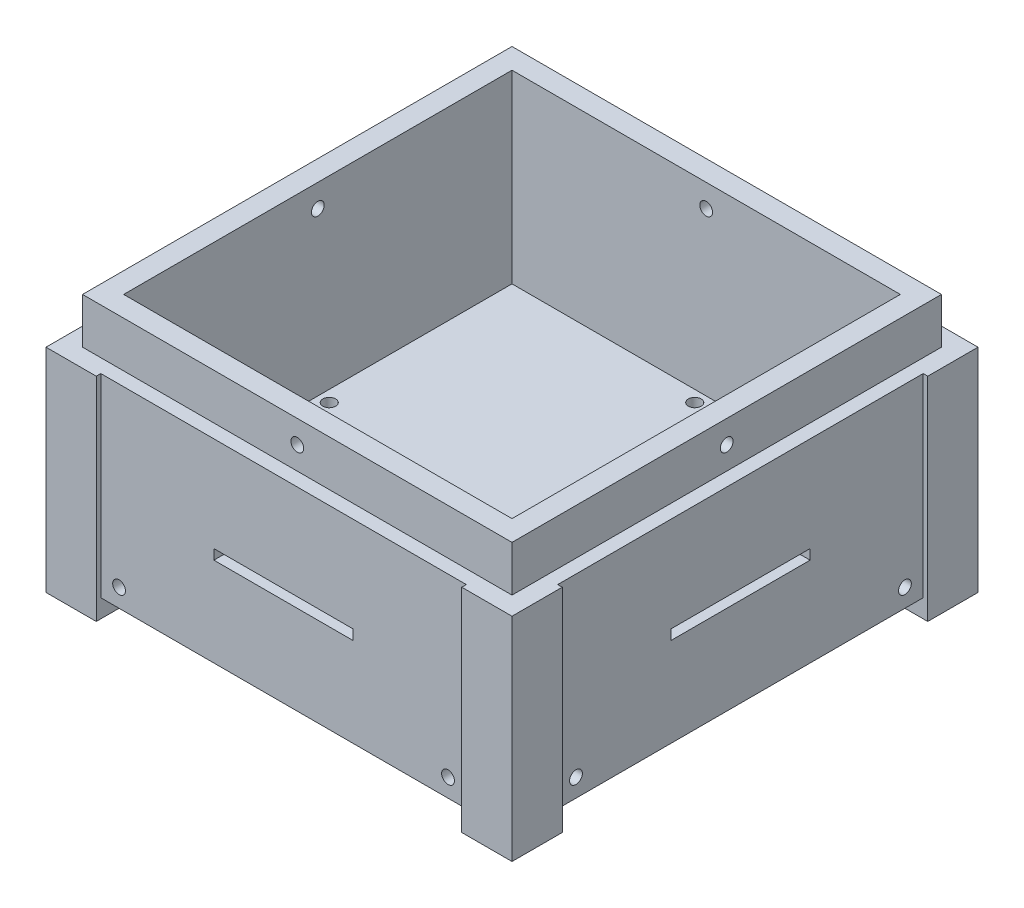
SolidWorks part; units mm, degrees
ref_plane "Front Plane" through (0, 0, 0) normal (0, 0, 1) x (1, 0, 0)
ref_plane "Top Plane" through (0, 0, 0) normal (0, 1, 0) x (1, 0, 0)
ref_plane "Right Plane" through (0, 0, 0) normal (1, 0, 0) x (0, 0, -1)
sketch "Sketch1" plane through (0, 0, 0) normal (0, 1, 0) x (1, 0, 0)
  line L1 (-50, 50) -> (50, 50)
  line L2 (-50, 50) -> (-50, -50)
  line L3 (-50, -50) -> (50, -50)
  line L4 (50, 50) -> (50, -50)
  line L5 (-50, 50) -> (50, -50) construction
  line L6 (-50, -50) -> (50, 50) construction
  point P0 (0, 0)
  dimension "D1" = 100
  dimension "D2" = 100
extrude "Boss-Extrude1" add sketch "Sketch1" along normal blind 95
ref_plane "Plane1" through (0, 100, 0) normal (0, 1, 0) x (1, 0, 0)
sketch "Sketch2" plane through (0, 100, 0) normal (0, 1, 0) x (1, 0, 0)
  line L0 (0, 0) -> (0, 71.0273) construction
  line L1 (-50, 50) -> (-40, 50)
  line L2 (-50, 50) -> (-50, 40)
  line L3 (-50, 40) -> (-40, 40)
  line L4 (-40, 50) -> (-40, 40)
  line L5 (50, 40) -> (40, 40)
  line L6 (40, 50) -> (40, 40)
  line L7 (50, 50) -> (40, 50)
  line L8 (50, 50) -> (50, 40)
  line L9 (0, 0) -> (-74.2097, 0) construction
  line L10 (50, -50) -> (50, -40)
  line L11 (50, -50) -> (40, -50)
  line L12 (40, -50) -> (40, -40)
  line L13 (50, -40) -> (40, -40)
  line L14 (-50, -40) -> (-40, -40)
  line L15 (-40, -50) -> (-40, -40)
  line L16 (-50, -50) -> (-40, -50)
  line L17 (-50, -50) -> (-50, -40)
  dimension "D1" = 10
  dimension "D2" = 10
extrude "Boss-Extrude2" add sketch "Sketch2" against normal blind 105
sketch "Sketch3" plane through (0, 95, 0) normal (0, 1, 0) x (1, 0, 0)
  line L0 (0, 0) -> (-55.4811, 0) construction
  line L1 (0, 0) -> (0, -56.887) construction
  line L3 (50, -40) -> (40, -40) construction
  circle A0 centre (-28, -45) radius 1.4
  circle A1 centre (28, -45) radius 1.4
  circle A2 centre (28, 45) radius 1.4
  circle A3 centre (-28, 45) radius 1.4
  dimension "D1" = 2.8
  dimension "D2" = 28
  dimension "D3" = 85
extrude "Cut-Extrude1" cut sketch "Sketch3" against normal blind 10
sketch "Sketch4" plane through (0, 100, 0) normal (0, 1, 0) x (1, 0, 0)
  line L0 (-50, 50) -> (-50, 40) construction
  line L1 (-40, 40) -> (-51, 40)
  line L2 (-40, 40) -> (-40, 51)
  line L3 (-40, 51) -> (-51, 51)
  line L4 (-51, 40) -> (-51, 51)
  line L5 (40, 50) -> (-40, 50) construction
  line L6 (0, 0) -> (0, 60.0537) construction
  line L7 (0, 0) -> (-61.4769, 0) construction
  line L8 (40, 51) -> (51, 51)
  line L9 (51, 40) -> (51, 51)
  line L10 (40, 40) -> (51, 40)
  line L11 (40, 40) -> (40, 51)
  line L12 (40, -40) -> (40, -51)
  line L13 (40, -40) -> (51, -40)
  line L14 (51, -40) -> (51, -51)
  line L15 (40, -51) -> (51, -51)
  line L16 (-40, -51) -> (-51, -51)
  line L17 (-51, -40) -> (-51, -51)
  line L18 (-40, -40) -> (-51, -40)
  line L19 (-40, -40) -> (-40, -51)
  dimension "D1" = 1
  dimension "D2" = 1
extrude "Boss-Extrude3" add sketch "Sketch4" against normal up to surface (105 mm away) up to face at (-45, -5, -45)
sketch "Sketch5" plane through (0, 0, 50) normal (0, 0, 1) x (1, 0, 0)
  line L0 (0, 95) -> (0, 43.7031) construction
  line L1 (-40, 95) -> (40, 95) construction
  line L2 (40, 47.5) -> (-59.8843, 47.5) construction
  line L3 (40, 0) -> (40, 95) construction
  line L4 (-40, 95) -> (-40, 0) construction
  circle A0 centre (-36, 91) radius 1.4
  circle A1 centre (36, 91) radius 1.4
  circle A2 centre (36, 4) radius 1.4
  circle A3 centre (-36, 4) radius 1.4
  dimension "D1" = 2.8
  dimension "D2" = 4
  dimension "D3" = 4
extrude "Cut-Extrude2" cut sketch "Sketch5" against normal blind 10
mirror "Mirror1" about plane through (0, 0, 0) normal (0, 0, 1) of "Cut-Extrude2"
sketch "Sketch6" plane through (-50, 0, 0) normal (-1, 0, 0) x (0, 0, 1)
  line L0 (-40, 95) -> (-40, 0) construction
  line L1 (-40, 95) -> (40, 95) construction
  line L2 (0, 95) -> (0, 40.4022) construction
  line L3 (-40, 47.5) -> (36.0105, 47.5) construction
  line L4 (-40, -5) -> (-40, 100) construction
  circle A0 centre (-36, 91) radius 1.4
  circle A1 centre (36, 91) radius 1.4
  circle A2 centre (36, 4) radius 1.4
  circle A3 centre (-36, 4) radius 1.4
  dimension "D1" = 2.8
  dimension "D2" = 4
  dimension "D3" = 4
extrude "Cut-Extrude3" cut sketch "Sketch6" against normal blind 10
mirror "Mirror2" about plane through (0, 0, 0) normal (1, 0, 0) of "Cut-Extrude3"
ref_plane "Plane2" through (0, 47.5, 0) normal (0, 1, 0) x (1, 0, 0)
mirror "Mirror3" about plane through (0, 47.5, 0) normal (0, 1, 0) of "Cut-Extrude1"
chamfer "Chamfer1" distance 1 angle 45 33 edges at (-45.5, -5, 51) (-40, -5, 45.5) (-45.5, -5, 40) (-51, -5, 45.5) (40, -5, 45.5) (45.5, -5, 51) (51, -5, 45.5) (45.5, -5, 40) (45.5, -5, -51) (40, -5, -45.5) (45.5, -5, -40) (51, -5, -45.5) (-40, -5, -45.5) (-45.5, -5, -51) (-51, -5, -45.5) (-45.5, -5, -40) (45.5, 100, 51) (40, 100, 45.5) (45.5, 100, 40) (51, 100, 45.5) (40, 100, -45.5) (45.5, 100, -51) (51, 100, -45.5) (45.5, 100, -40) (-45.5, 100, -40) (-51, 100, -45.5) (-45.5, 100, -51) (-40, 100, -45.5) (-40, 100, 45.5) (-45.5, 100, 51) (-51, 100, 45.5) (-45.5, 100, 40) (45, 95, -40)
sketch "Sketch7" plane through (0, 95, 0) normal (0, 1, 0) x (1, 0, 0)
  line L0 (9.5, 4.5) -> (9.5, -38.5)
  line L1 (-8, 3) -> (8, 3)
  line L2 (-8, 3) -> (-8, -37)
  line L3 (-8, -37) -> (8, -37)
  line L4 (8, 3) -> (8, -37)
  line L5 (-9.5, -38.5) -> (9.5, -38.5)
  line L6 (-9.5, 4.5) -> (-9.5, -38.5)
  line L7 (-9.5, 4.5) -> (9.5, 4.5)
  dimension "D1" = 8
  dimension "D2" = 8
  dimension "D3" = 3
  dimension "D4" = 40
  dimension "D5" = 1.5
extrude "Boss-Extrude4" add sketch "Sketch7" along normal blind 3
sketch "Sketch8" plane through (0, 95, 0) normal (0, 1, 0) x (1, 0, 0)
  line L4 (-8, 3) -> (-8, -37)
  line L5 (-8, -37) -> (8, -37)
  line L6 (8, -37) -> (8, 3)
  line L7 (8, 3) -> (-8, 3)
  line L8 (-8, 3) -> (-8, -37)
  line L9 (-8, -37) -> (8, -37)
  line L10 (8, -37) -> (8, 3)
  line L11 (8, 3) -> (-8, 3)
  dimension "D1" = 0
extrude "Cut-Extrude4" cut sketch "Sketch8" against normal blind 10
chamfer "Chamfer2" distance 13 angle 45 1 edges at (0, 85, 37)
sketch "Sketch9" plane through (0, 85, 0) normal (0, 1, 0) x (1, 0, 0)
  line L0 (8, -24) -> (8, 3) construction
  line L1 (-8, 3) -> (8, 3)
  line L2 (-8, 3) -> (-8, -0.1)
  line L3 (-8, -0.1) -> (8, -0.1)
  line L4 (8, 3) -> (8, -0.1)
  dimension "D1" = 3.1
extrude "Cut-Extrude5" cut sketch "Sketch9" against normal blind 10
fillet "Fillet1" radius 1 1 edges at (0, 85, 0.1)
sketch "Sketch10" plane through (0, 0, -3) normal (0, 0, 1) x (1, 0, 0)
  line L0 (8, 98) -> (-8, 98) construction
  line L1 (-8, 98) -> (-8, 75) construction
  circle A0 centre (0, 92) radius 1.4
  dimension "D1" = 2.8
  dimension "D2" = 6
  dimension "D3" = 8
extrude "Cut-Extrude6" cut sketch "Sketch10" against normal blind 10
sketch "Sketch12" plane through (-50, 0, 0) normal (-1, 0, 0) x (0, 0, 1)
  line L0 (-40, 95) -> (40, 95) construction
  line L1 (-15.25, 75.5) -> (15.25, 75.5)
  line L2 (-15.25, 75.5) -> (-15.25, 73.3)
  line L3 (-15.25, 73.3) -> (15.25, 73.3)
  line L4 (15.25, 75.5) -> (15.25, 73.3)
  line L5 (-15.25, 75.5) -> (15.25, 73.3) construction
  line L6 (-15.25, 73.3) -> (15.25, 75.5) construction
  line L7 (0, 95) -> (0, 60.126) construction
  line L8 (-51, 47.5) -> (62.2361, 47.5) construction
  line L9 (-51, -4) -> (-51, 99) construction
  line L10 (-15.25, 21.7) -> (15.25, 21.7)
  line L11 (15.25, 19.5) -> (15.25, 21.7)
  line L12 (-15.25, 19.5) -> (15.25, 19.5)
  line L13 (-15.25, 19.5) -> (-15.25, 21.7)
  line L14 (-40, 0) -> (40, 0) construction
  point P0 (0, 74.4)
  dimension "D1" = 19.5
  dimension "D2" = 2.2
  dimension "D3" = 30.5
extrude "Cut-Extrude7" cut sketch "Sketch12" against normal blind 3
mirror "Mirror4" about plane through (0, 0, 0) normal (1, 0, 0) of "Cut-Extrude7"
sketch "Sketch13" plane through (0, 0, 50) normal (0, 0, 1) x (1, 0, 0)
  line L0 (0, 95) -> (0, 46.2553) construction
  line L1 (-40, 95) -> (40, 95) construction
  line L2 (-51, 47.5) -> (61.8656, 47.5) construction
  line L3 (-15.25, 75.5) -> (15.25, 75.5)
  line L4 (-15.25, 75.5) -> (-15.25, 73.3)
  line L5 (-15.25, 73.3) -> (15.25, 73.3)
  line L6 (15.25, 75.5) -> (15.25, 73.3)
  line L7 (-15.25, 75.5) -> (15.25, 73.3) construction
  line L8 (-15.25, 73.3) -> (15.25, 75.5) construction
  line L9 (-51, -4) -> (-51, 99) construction
  line L10 (-15.25, 21.7) -> (15.25, 21.7)
  line L11 (15.25, 19.5) -> (15.25, 21.7)
  line L12 (-15.25, 19.5) -> (15.25, 19.5)
  line L13 (-15.25, 19.5) -> (-15.25, 21.7)
  point P5 (0, 74.4)
  dimension "D1" = 30.5
  dimension "D2" = 2.2
  dimension "D3" = 19.5
extrude "Cut-Extrude8" cut sketch "Sketch13" against normal blind 3
mirror "Mirror5" about plane through (0, 0, 0) normal (0, 0, 1) of "Cut-Extrude8"
sketch "Sketch14" plane through (0, 95, 0) normal (0, 1, 0) x (1, 0, 0)
  line L0 (-50, 0) -> (73.3052, 0) construction
  line L1 (-50, 40) -> (-50, -40) construction
  line L2 (0, 50) -> (0, -6.1969) construction
  line L3 (40, 50) -> (-40, 50) construction
  line L4 (28, 15.25) -> (25.8, 15.25)
  line L5 (-28, -15.25) -> (-25.8, -15.25)
  line L6 (-28, -15.25) -> (-28, 15.25)
  line L7 (-28, 15.25) -> (-25.8, 15.25)
  line L8 (-25.8, -15.25) -> (-25.8, 15.25)
  line L9 (-28, -15.25) -> (-25.8, 15.25) construction
  line L10 (-28, 15.25) -> (-25.8, -15.25) construction
  line L11 (25.8, -15.25) -> (25.8, 15.25)
  line L12 (28, -15.25) -> (25.8, -15.25)
  line L13 (28, -15.25) -> (28, 15.25)
  point P9 (-26.9, 0)
  dimension "D1" = 30.5
  dimension "D2" = 2.2
  dimension "D3" = 22
extrude "Cut-Extrude9" cut sketch "Sketch14" against normal blind 3
mirror "Mirror6" about plane through (0, 47.5, 0) normal (0, 1, 0) of "Cut-Extrude9"
sketch "Sketch15" plane through (0, 0, 0) normal (1, 0, 0) x (0, 0, -1)
  line L0 (-40, 0) -> (40, 0) construction
  line L1 (-45, 70) -> (45, 70)
  line L2 (-45, 70) -> (-45, 12)
  line L3 (-45, 12) -> (45, 12)
  line L4 (45, 70) -> (45, 12)
  line L5 (-45, 70) -> (45, 12) construction
  line L6 (-45, 12) -> (45, 70) construction
  line L7 (-51, -4) -> (-51, 99) construction
  line L8 (51, -4) -> (51, 99) construction
  line L9 (-40, 95) -> (39, 95) construction
  point P0 (0, 41)
  dimension "D1" = 12
  dimension "D2" = 6
  dimension "D3" = 6
  dimension "D4" = 25
extrude "Cut-Extrude10" cut sketch "Sketch15" against normal offset from surface 6 and the other way offset from surface 6 up to face at (-51, 47.5, -45.5) other way up to face at (51, 47.5, 45.5)
sketch "Sketch16" plane through (0, 0, 0) normal (0, 0, 1) x (1, 0, 0)
  line L0 (45, 57.0064) -> (-45, 57.0064)
  line L1 (51, -4) -> (51, 99) construction
  line L2 (-51, -4) -> (-51, 99) construction
  line L3 (45, 57.0064) -> (45, 83)
  line L4 (45, 83) -> (13, 83)
  line L5 (13, 83) -> (13, 67.0064)
  line L6 (13, 67.0064) -> (-13, 67.0064)
  line L7 (-13, 67.0064) -> (-13, 83)
  line L8 (-13, 83) -> (-45, 83)
  line L9 (-45, 83) -> (-45, 57.0064)
  line L10 (-40, 95) -> (40, 95) construction
  dimension "D1" = 6
  dimension "D2" = 6
  dimension "D3" = 57.0064
  dimension "D4" = 12
  dimension "D5" = 32
  dimension "D7" = 10
extrude "Cut-Extrude11" cut sketch "Sketch16" along normal up to surface and the other way up to surface up to face at (0, 41, 45) other way up to face at (0, 41, -45)
chamfer "Chamfer3" distance 4 angle 45 2 edges at (-13, 70, 0) (13, 70, 0)
sketch "Sketch17" plane through (0, 0, -51) normal (0, 0, -1) x (-1, 0, 0)
  line L0 (-51, -4) -> (-51, 99) construction
  line L2 (-51, 47.5) -> (-51, 104.9128)
  line L3 (-51, 104.9128) -> (51, 104.9128)
  line L4 (51, 47.5) -> (51, 104.9128)
  line L6 (40, -4) -> (51, -4) construction
  line L7 (-51, 47.5) -> (-51, 42.5)
  line L8 (-51, 42.5) -> (51, 42.5)
  line L9 (51, -4) -> (51, 99) construction
  line L10 (51, 42.5) -> (51, 47.5)
  dimension "D2" = 108.9128
  dimension "D3" = 46.5
extrude "Cut-Extrude12" cut sketch "Sketch17" against normal through all
sketch "Sketch19" plane through (0, 42.5, 0) normal (0, 1, 0) x (1, 0, 0)
  line L1 (-47, -47) -> (47, -47)
  line L2 (-47, -47) -> (-47, 47)
  line L3 (-47, 47) -> (47, 47)
  line L4 (47, -47) -> (47, 47)
  line L5 (-47, -47) -> (47, 47) construction
  line L6 (-47, 47) -> (47, -47) construction
  line L7 (-42.5, 42.5) -> (42.5, 42.5)
  line L8 (-42.5, 42.5) -> (-42.5, -42.5)
  line L9 (-42.5, -42.5) -> (42.5, -42.5)
  line L10 (42.5, 42.5) -> (42.5, -42.5)
  line L11 (-42.5, 42.5) -> (42.5, -42.5) construction
  line L12 (-42.5, -42.5) -> (42.5, 42.5) construction
  point P0 (0, 0)
  point P6 (0, 0)
  dimension "D1" = 94
  dimension "D2" = 94
  dimension "D3" = 85
  dimension "D4" = 85
extrude "Boss-Extrude7" add sketch "Sketch19" against normal up to surface (30.5 mm away) and the other way blind 10 up to face at (0, 12, 0)
sketch "Sketch20" plane through (0, 0, 47) normal (0, 0, 1) x (1, 0, 0)
  line L0 (-47, 52.5) -> (47, 52.5) construction
  line L1 (-47, 52.5) -> (-47, 42.5) construction
  circle A0 centre (0, 47.5) radius 1.4
  dimension "D1" = 2.8
  dimension "D2" = 5
  dimension "D3" = 47
extrude "Cut-Extrude13" cut sketch "Sketch20" against normal through all
sketch "Sketch21" plane through (47, 0, 0) normal (1, 0, 0) x (0, 0, -1)
  line L0 (-47, 52.5) -> (47, 52.5) construction
  line L1 (-47, 52.5) -> (-47, 42.5) construction
  circle A0 centre (0, 47.5) radius 1.4
  dimension "D1" = 2.8
  dimension "D2" = 5
  dimension "D3" = 47
extrude "Cut-Extrude14" cut sketch "Sketch21" against normal through all
sketch "Sketch22" plane through (0, 0, 0) normal (0, -1, 0) x (1, 0, 0)
  line L0 (28, -15.25) -> (28, 15.25) construction
  line L1 (28, 15.25) -> (25.8, 15.25) construction
  line L2 (25.8, 15.25) -> (25.8, -15.25) construction
  line L3 (25.8, -15.25) -> (28, -15.25) construction
  line L4 (-25.8, -15.25) -> (-25.8, 15.25) construction
  line L5 (-25.8, 15.25) -> (-28, 15.25) construction
  line L6 (-28, 15.25) -> (-28, -15.25) construction
  line L7 (-28, -15.25) -> (-25.8, -15.25) construction
  line L8 (28, -15.25) -> (28, 15.25)
  line L9 (28, 15.25) -> (25.8, 15.25)
  line L10 (25.8, 15.25) -> (25.8, -15.25)
  line L11 (25.8, -15.25) -> (28, -15.25)
  line L12 (-25.8, -15.25) -> (-25.8, 15.25)
  line L13 (-25.8, 15.25) -> (-28, 15.25)
  line L14 (-28, 15.25) -> (-28, -15.25)
  line L15 (-28, -15.25) -> (-25.8, -15.25)
extrude "Boss-Extrude8" add sketch "Sketch22" against normal up to surface (3 mm away) up to face at (-26.9, 3, 0)
sketch "Sketch23" plane through (0, 0, 0) normal (0, -1, 0) x (1, 0, 0)
  circle A0 centre (0, 0) radius 40 construction
  circle A1 centre (-40, 0) radius 1.4
  circle A2 centre (0, 40) radius 1.4
  circle A3 centre (40, 0) radius 1.4
  circle A4 centre (0, -40) radius 1.4
  point P14 (0, 0)
  dimension "D1" = 80
  dimension "D2" = 2.8
  dimension "D3" = 4
extrude "Cut-Extrude15" cut sketch "Sketch23" against normal blind 20
